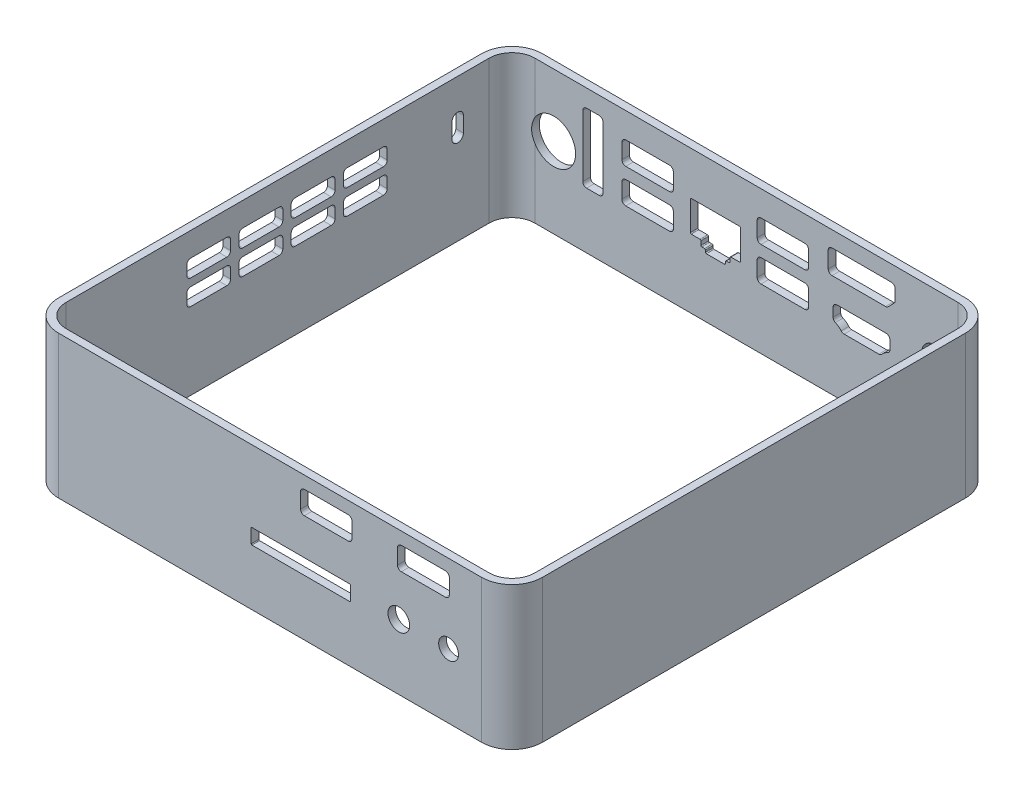
SolidWorks part; units mm, degrees
ref_plane "Front Plane" through (0, 0, 0) normal (0, 0, 1) x (1, 0, 0)
ref_plane "Top Plane" through (0, 0, 0) normal (0, 1, 0) x (1, 0, 0)
ref_plane "Right Plane" through (0, 0, 0) normal (1, 0, 0) x (0, 0, -1)
sketch "Sketch1" plane through (0, 0, 0) normal (0, 1, 0) x (1, 0, 0)
  line L0 (2, 8) -> (2, 119)
  line L1 (8, 0) -> (119, 0)
  line L2 (0, 8) -> (0, 119)
  line L3 (8, 127) -> (119, 127)
  line L4 (127, 8) -> (127, 119)
  line L5 (8, 125) -> (119, 125)
  line L6 (125, 8) -> (125, 119)
  line L7 (8, 2) -> (119, 2)
  arc A0 (119, 0) -> (127, 8) centre (119, 8) ccw
  arc A1 (8, 0) -> (0, 8) centre (8, 8) cw
  arc A2 (119, 127) -> (127, 119) centre (119, 119) cw
  arc A3 (0, 119) -> (8, 127) centre (8, 119) cw
  arc A4 (2, 119) -> (8, 125) centre (8, 119) cw
  arc A5 (119, 125) -> (125, 119) centre (119, 119) cw
  arc A6 (119, 2) -> (125, 8) centre (119, 8) ccw
  arc A7 (8, 2) -> (2, 8) centre (8, 8) cw
  point P9 (0, 0)
  dimension "D3" = 8
  dimension "D1" = 127
  dimension "D2" = 127
  dimension "D4" = 2
extrude "Boss-Extrude1" add sketch "Sketch1" along normal blind 37.5
sketch "Sketch12" plane through (0, 0, 0) normal (1, 0, 0) x (0, 0, -1)
  line L1 (40.65, 31.2) -> (50.15, 31.2)
  line L2 (39.65, 30.2) -> (39.65, 27.7)
  line L3 (40.65, 26.7) -> (50.15, 26.7)
  line L4 (51.15, 30.2) -> (51.15, 27.7)
  arc A0 (39.65, 27.7) -> (40.65, 26.7) centre (40.65, 27.7) ccw
  arc A1 (50.15, 26.7) -> (51.15, 27.7) centre (50.15, 27.7) ccw
  arc A2 (50.15, 31.2) -> (51.15, 30.2) centre (50.15, 30.2) cw
  arc A3 (40.65, 31.2) -> (39.65, 30.2) centre (40.65, 30.2) ccw
  dimension "D5" = 1
  dimension "D1" = 39.65
  dimension "D2" = 11.5
  dimension "D3" = 26.7
  dimension "D4" = 4.5
extrude "Cut-Extrude2" cut sketch "Sketch12" along normal up to next
pattern_linear "LPattern1" count 2 spacing 6.5 along (0, -1, 0) count 4 spacing 13.7 along (0, 0, -1) of "Cut-Extrude2"
sketch "Sketch18" plane through (0, 0, 0) normal (-1, 0, 0) x (0, 0, 1)
  line L0 (-110.75, 23.85) -> (-110.75, 27.85) construction
  line L1 (-112.25, 23.85) -> (-112.25, 27.85)
  line L2 (-109.25, 23.85) -> (-109.25, 27.85)
  line L3 (-119, 37.5) -> (-8, 37.5) construction
  line L4 (-127, 37.5) -> (-127, 0) construction
  arc A0 (-112.25, 23.85) -> (-109.25, 23.85) centre (-110.75, 23.85) ccw
  arc A1 (-109.25, 27.85) -> (-112.25, 27.85) centre (-110.75, 27.85) ccw
  point P2 (-110.75, 25.85)
  dimension "D2" = 1.5
  dimension "D1" = 4
  dimension "D3" = 9.65
  dimension "D4" = 16.25
extrude "Cut-Extrude8" cut sketch "Sketch18" against normal up to next
sketch "Sketch15" plane through (0, 0, 0) normal (0, 0, 1) x (1, 0, 0)
  line L0 (0, 37.5) -> (0, 0) construction
  line L1 (84.45, 18.7) -> (58.75, 18.7)
  line L2 (84.65, 18.5) -> (84.65, 14.9)
  line L3 (84.45, 14.7) -> (58.75, 14.7)
  line L4 (58.55, 18.5) -> (58.55, 14.9)
  line L5 (72.5, 34.25) -> (84, 34.25)
  line L6 (71.5, 33.25) -> (71.5, 29.25)
  line L7 (72.5, 28.25) -> (84, 28.25)
  line L8 (85, 33.25) -> (85, 29.25)
  line L9 (97.95, 34.25) -> (109.55, 34.25)
  line L10 (96.95, 33.25) -> (96.95, 29.25)
  line L11 (97.95, 28.25) -> (109.55, 28.25)
  line L12 (110.55, 33.25) -> (110.55, 29.25)
  line L14 (8, 0) -> (119, 0) construction
  line L15 (8, 37.5) -> (119, 37.5) construction
  circle A0 centre (97.3, 17.1) radius 2.85
  circle A1 centre (110.35, 16.9) radius 2.6
  arc A2 (84, 28.25) -> (85, 29.25) centre (84, 29.25) ccw
  arc A3 (84, 34.25) -> (85, 33.25) centre (84, 33.25) cw
  arc A4 (72.5, 34.25) -> (71.5, 33.25) centre (72.5, 33.25) ccw
  arc A5 (71.5, 29.25) -> (72.5, 28.25) centre (72.5, 29.25) ccw
  arc A6 (84.65, 14.9) -> (84.45, 14.7) centre (84.45, 14.9) cw
  arc A7 (84.45, 18.7) -> (84.65, 18.5) centre (84.45, 18.5) cw
  arc A8 (58.75, 14.7) -> (58.55, 14.9) centre (58.75, 14.9) cw
  arc A9 (58.75, 18.7) -> (58.55, 18.5) centre (58.75, 18.5) ccw
  arc A10 (96.95, 29.25) -> (97.95, 28.25) centre (97.95, 29.25) ccw
  arc A11 (109.55, 28.25) -> (110.55, 29.25) centre (109.55, 29.25) ccw
  arc A12 (109.55, 34.25) -> (110.55, 33.25) centre (109.55, 33.25) cw
  arc A13 (97.95, 34.25) -> (96.95, 33.25) centre (97.95, 33.25) ccw
  dimension "D13" = 5.7
  dimension "D14" = 5.2
  dimension "D15" = 1
  dimension "D3" = 1
  dimension "D2" = 0.2
  dimension "D4" = 13.6
  dimension "D5" = 13.5
  dimension "D6" = 6
  dimension "D7" = 6
  dimension "D8" = 26.1
  dimension "D9" = 4
  dimension "D10" = 58.55
  dimension "D11" = 71.5
  dimension "D12" = 96.95
  dimension "D16" = 97.3
  dimension "D17" = 110.35
  dimension "D18" = 16.9
  dimension "D19" = 17.1
  dimension "D20" = 14.7
  dimension "D21" = 3.25
  dimension "D22" = 3.25
extrude "Cut-Extrude5" cut sketch "Sketch15" against normal blind 2
sketch "Sketch16" plane through (0, 0, -127) normal (0, 0, -1) x (-1, 0, 0)
  line L0 (-100.162, 21.0556) -> (-87.262, 21.0556)
  line L1 (-86.262, 20.0556) -> (-86.262, 17.7485)
  line L2 (-89.1527, 15.3556) -> (-98.2712, 15.3556)
  line L3 (-101.162, 17.7485) -> (-101.162, 20.0556)
  line L4 (-101.5483, 33.3493) -> (-85.9787, 33.3493)
  line L5 (-78.8419, 30.8312) -> (-67.3419, 30.8312)
  line L6 (-79.8419, 29.8312) -> (-79.8419, 25.8312)
  line L7 (-78.8419, 24.8312) -> (-67.3419, 24.8312)
  line L8 (-66.3419, 29.8312) -> (-66.3419, 25.8312)
  line L9 (-24.8661, 32.9015) -> (-21.5749, 32.9015)
  line L10 (-25.8661, 31.9015) -> (-25.8661, 15.7374)
  line L11 (-24.8661, 14.7374) -> (-21.5749, 14.7374)
  line L12 (-20.5749, 31.9015) -> (-20.5749, 15.7374)
  line L13 (-84.9787, 32.3493) -> (-84.9787, 28.0682)
  line L14 (-85.9787, 27.0682) -> (-100.024, 27.0682)
  line L15 (-100.7372, 27.3673) -> (-102.2616, 28.9183)
  line L16 (-102.5483, 29.6193) -> (-102.5483, 32.3493)
  line L17 (-61.736, 26.1367) -> (-49.037, 26.1367)
  line L18 (-48.787, 25.8867) -> (-48.787, 18.2544)
  line L19 (-49.037, 18.0044) -> (-51.332, 18.0044)
  line L20 (-51.582, 17.7544) -> (-51.582, 16.7547)
  line L21 (-51.832, 16.5047) -> (-52.5205, 16.5047)
  line L22 (-52.7705, 16.2547) -> (-52.7705, 15.7891)
  line L23 (-53.0205, 15.5391) -> (-57.7525, 15.5391)
  line L24 (-58.0025, 15.7891) -> (-58.0025, 16.2547)
  line L25 (-58.2525, 16.5047) -> (-58.941, 16.5047)
  line L26 (-59.191, 16.7547) -> (-59.191, 17.7544)
  line L27 (-59.441, 18.0044) -> (-61.736, 18.0044)
  line L28 (-61.986, 18.2544) -> (-61.986, 25.8867)
  circle A0 centre (-113.0051, 21.3213) radius 3.5
  arc A1 (-86.866, 16.8303) -> (-88.3931, 15.7052) centre (-85.2027, 12.9737) ccw
  arc A2 (-99.0308, 15.7052) -> (-100.558, 16.8303) centre (-102.2212, 12.9737) ccw
  circle A3 centre (-12.946, 21.0556) radius 5.75
  arc A4 (-21.5749, 14.7374) -> (-20.5749, 15.7374) centre (-21.5749, 15.7374) ccw
  arc A5 (-25.8661, 15.7374) -> (-24.8661, 14.7374) centre (-24.8661, 15.7374) ccw
  arc A6 (-24.8661, 32.9015) -> (-25.8661, 31.9015) centre (-24.8661, 31.9015) ccw
  arc A7 (-67.3419, 30.8312) -> (-66.3419, 29.8312) centre (-67.3419, 29.8312) cw
  arc A8 (-67.3419, 24.8312) -> (-66.3419, 25.8312) centre (-67.3419, 25.8312) ccw
  arc A9 (-79.8419, 25.8312) -> (-78.8419, 24.8312) centre (-78.8419, 25.8312) ccw
  arc A10 (-78.8419, 30.8312) -> (-79.8419, 29.8312) centre (-78.8419, 29.8312) ccw
  arc A11 (-100.558, 16.8303) -> (-101.162, 17.7485) centre (-100.162, 17.7485) cw
  arc A12 (-98.2712, 15.3556) -> (-99.0308, 15.7052) centre (-98.2712, 16.3556) cw
  arc A13 (-88.3931, 15.7052) -> (-89.1527, 15.3556) centre (-89.1527, 16.3556) cw
  arc A14 (-86.262, 17.7485) -> (-86.866, 16.8303) centre (-87.262, 17.7485) cw
  arc A15 (-87.262, 21.0556) -> (-86.262, 20.0556) centre (-87.262, 20.0556) cw
  arc A16 (-100.162, 21.0556) -> (-101.162, 20.0556) centre (-100.162, 20.0556) ccw
  arc A17 (-21.5749, 32.9015) -> (-20.5749, 31.9015) centre (-21.5749, 31.9015) cw
  arc A18 (-100.024, 27.0682) -> (-100.7372, 27.3673) centre (-100.024, 28.0682) cw
  arc A19 (-84.9787, 28.0682) -> (-85.9787, 27.0682) centre (-85.9787, 28.0682) cw
  arc A20 (-85.9787, 33.3493) -> (-84.9787, 32.3493) centre (-85.9787, 32.3493) cw
  arc A21 (-101.5483, 33.3493) -> (-102.5483, 32.3493) centre (-101.5483, 32.3493) ccw
  arc A22 (-102.2616, 28.9183) -> (-102.5483, 29.6193) centre (-101.5483, 29.6193) cw
  arc A23 (-61.736, 18.0044) -> (-61.986, 18.2544) centre (-61.736, 18.2544) cw
  arc A24 (-59.191, 17.7544) -> (-59.441, 18.0044) centre (-59.441, 17.7544) ccw
  arc A25 (-58.941, 16.5047) -> (-59.191, 16.7547) centre (-58.941, 16.7547) cw
  arc A26 (-58.0025, 16.2547) -> (-58.2525, 16.5047) centre (-58.2525, 16.2547) ccw
  arc A27 (-57.7525, 15.5391) -> (-58.0025, 15.7891) centre (-57.7525, 15.7891) cw
  arc A28 (-52.7705, 15.7891) -> (-53.0205, 15.5391) centre (-53.0205, 15.7891) cw
  arc A29 (-52.5205, 16.5047) -> (-52.7705, 16.2547) centre (-52.5205, 16.2547) ccw
  arc A30 (-51.582, 16.7547) -> (-51.832, 16.5047) centre (-51.832, 16.7547) cw
  arc A31 (-51.332, 18.0044) -> (-51.582, 17.7544) centre (-51.332, 17.7544) ccw
  arc A32 (-48.787, 18.2544) -> (-49.037, 18.0044) centre (-49.037, 18.2544) cw
  arc A33 (-49.037, 26.1367) -> (-48.787, 25.8867) centre (-49.037, 25.8867) cw
  arc A34 (-61.736, 26.1367) -> (-61.986, 25.8867) centre (-61.736, 25.8867) ccw
  point P40 (-98.762, 15.3556)
  point P43 (-88.662, 15.3556)
  dimension "D1" = 7
  dimension "D5" = 4.2
  dimension "D6" = 11.5
  dimension "D7" = 1
  dimension "D8" = 1
  dimension "D9" = 0.25
  dimension "D2" = 2.4
  dimension "D3" = 2.4
  dimension "D4" = 5.7
  dimension "D10" = 14.9
  dimension "D11" = 6
  dimension "D12" = 13.5
extrude "Cut-Extrude6" cut sketch "Sketch16" against normal up to next
pattern_linear "LPattern2" count 2 spacing 35.5 along (-1, 0, 0) count 2 spacing 9 along (0, -1, 0) of face at (73.0919, 24.8312, -126) of face at (66.7384, 25.2276, -126) of face at (66.3419, 27.8312, -126) of face at (66.7384, 30.4348, -126) of face at (73.0919, 30.8312, -126) of face at (79.4455, 30.4348, -126) of face at (79.8419, 27.8312, -126) of face at (79.4455, 25.2276, -126)
